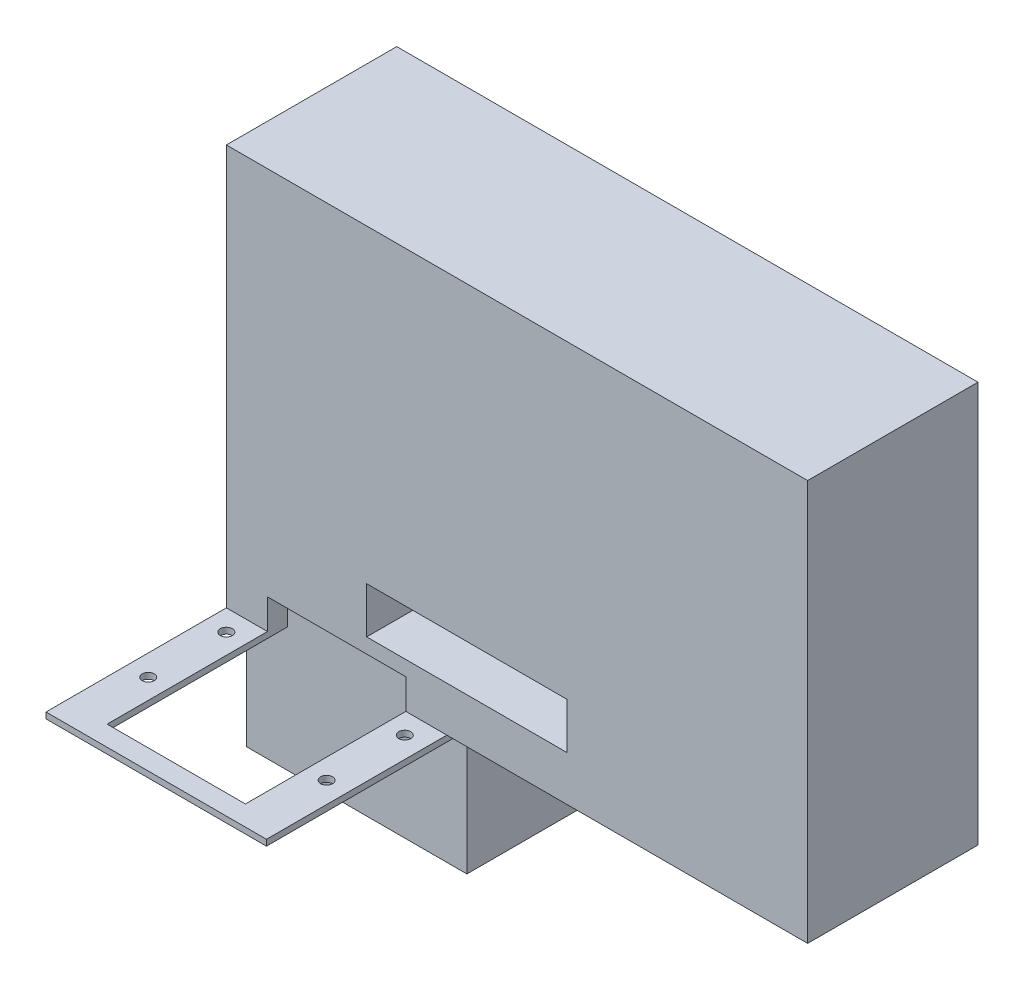
SolidWorks part; units mm, degrees
material "Cedro"
ref_plane "Alzado" through (0, 0, 0) normal (0, 0, 1) x (1, 0, 0)
ref_plane "Planta" through (0, 0, 0) normal (0, 1, 0) x (1, 0, 0)
ref_plane "Vista lateral" through (0, 0, 0) normal (1, 0, 0) x (0, 0, -1)
sketch "Croquis1" plane through (0, 0, 0) normal (0, 0, 1) x (1, 0, 0)
  line L1 (-85.6349, 58.6584) -> (24.3651, 58.6584)
  line L2 (-85.6349, 58.6584) -> (-85.6349, -6.3416)
  line L3 (-85.6349, -6.3416) -> (24.3651, -6.3416)
  line L4 (24.3651, 58.6584) -> (24.3651, -6.3416)
  line L5 (-85.6349, 58.6584) -> (24.3651, -6.3416) construction
  line L6 (-85.6349, -6.3416) -> (24.3651, 58.6584) construction
  point P0 (-30.6349, 26.1584)
  dimension "D1" = 65
  dimension "D2" = 110
extrude "Saliente-Extruir1" add sketch "Croquis1" along normal blind 75
sketch "Croquis3" plane through (0, 0, 75) normal (0, 0, 1) x (1, 0, 0)
  line L0 (-85.6349, 58.6584) -> (24.3651, 58.6584)
  line L1 (-85.6349, 58.6584) -> (-85.6349, 55.6584)
  line L2 (-85.6349, 58.6584) -> (-85.6349, -6.3416) construction
  line L3 (-85.6349, 55.6584) -> (24.3651, 55.6584)
  line L4 (24.3651, -6.3416) -> (24.3651, 58.6584) construction
  line L5 (24.3651, 55.6584) -> (24.3651, 58.6584)
  dimension "D1" = 3
extrude "Saliente-Extruir2" add sketch "Croquis3" along normal blind 70
sketch "Croquis4" plane through (0, 55.6584, 0) normal (0, -1, 0) x (1, 0, 0)
  line L3 (-65.1349, 134.5) -> (-65.1349, 75)
  line L6 (-85.6349, 75) -> (24.3651, 75) construction
  line L7 (-65.1349, 134.5) -> (-65.1349, 145)
  line L8 (-85.6349, 145) -> (24.3651, 145) construction
  line L9 (-65.1349, 75) -> (3.8651, 75)
  line L11 (-65.1349, 145) -> (3.8651, 145)
  line L13 (3.8651, 138) -> (3.8651, 145)
  line L14 (3.8651, 138) -> (3.8651, 75)
  circle A0 centre (-75.1349, 134.5) radius 3
  circle A1 centre (-75.1349, 95.5) radius 3
  circle A2 centre (13.8651, 134.5) radius 3
  circle A3 centre (13.8651, 95.5) radius 3
  dimension "D5" = 6
  dimension "D6" = 6
  dimension "D7" = 6
  dimension "D8" = 6
  dimension "D1" = 10
  dimension "D3" = 39
  dimension "D4" = 89
extrude "Cortar-Extruir1" cut sketch "Croquis4" against normal blind 70
sketch "Croquis6" plane through (0, 58.6584, 0) normal (0, 1, 0) x (1, 0, 0)
  line L0 (-85.6349, -145) -> (-85.6349, -175)
  line L1 (-85.6349, -175) -> (24.3651, -175)
  line L2 (24.3651, -175) -> (24.3651, -145)
  line L3 (24.3651, -145) -> (3.8651, -145)
  line L4 (-65.1349, -145) -> (-65.1349, -165)
  line L5 (-65.1349, -165) -> (3.8651, -165)
  line L6 (3.8651, -165) -> (3.8651, -145)
  line L7 (-65.1349, -145) -> (-85.6349, -145)
  dimension "D1" = 30
  dimension "D2" = 20
extrude "Saliente-Extruir3" add sketch "Croquis6" against normal blind 3
sketch "Croquis7" plane through (0, 58.6584, 0) normal (0, 1, 0) x (1, 0, 0)
  line L0 (-85.6349, 0) -> (204.3651, 0)
  line L1 (-85.6349, 0) -> (-85.6349, -85)
  line L2 (-85.6349, -175) -> (-85.6349, 0) construction
  line L3 (-85.6349, -85) -> (204.3651, -85)
  line L4 (204.3651, -85) -> (204.3651, 0)
  dimension "D1" = 290
  dimension "D2" = 85
extrude "Saliente-Extruir4" add sketch "Croquis7" along normal blind 200
sketch "Croquis8" plane through (0, 0, 85) normal (0, 0, 1) x (1, 0, 0)
  line L0 (-65.1349, 58.6584) -> (-65.1349, 73.6584)
  line L1 (-65.1349, 73.6584) -> (3.8651, 73.6584)
  line L2 (3.8651, 58.6584) -> (3.8651, 73.6584)
  line L3 (-65.1349, 58.6584) -> (3.8651, 58.6584)
  dimension "D1" = 15
  dimension "D2" = 15
extrude "Cortar-Extruir2" cut sketch "Croquis8" against normal blind 10
sketch "Croquis10" plane through (0, 0, 85) normal (0, 0, 1) x (1, 0, 0)
  line L1 (-0.6349, 81.0942) -> (-15.6349, 81.0942)
  line L2 (69.3651, 81.0942) -> (-0.6349, 81.0942)
  line L4 (-15.6349, 81.0942) -> (-15.6349, 104.0942)
  line L5 (-15.6349, 104.0942) -> (-0.6349, 104.0942)
  line L6 (69.3651, 81.0942) -> (84.3651, 81.0942)
  line L7 (69.3651, 104.0942) -> (-0.6349, 104.0942)
  line L8 (84.3651, 81.0942) -> (84.3651, 104.0942)
  line L11 (84.3651, 104.0942) -> (69.3651, 104.0942)
  dimension "D1" = 15
  dimension "D3" = 15
extrude "Cortar-Extruir3" cut sketch "Croquis10" against normal blind 50
